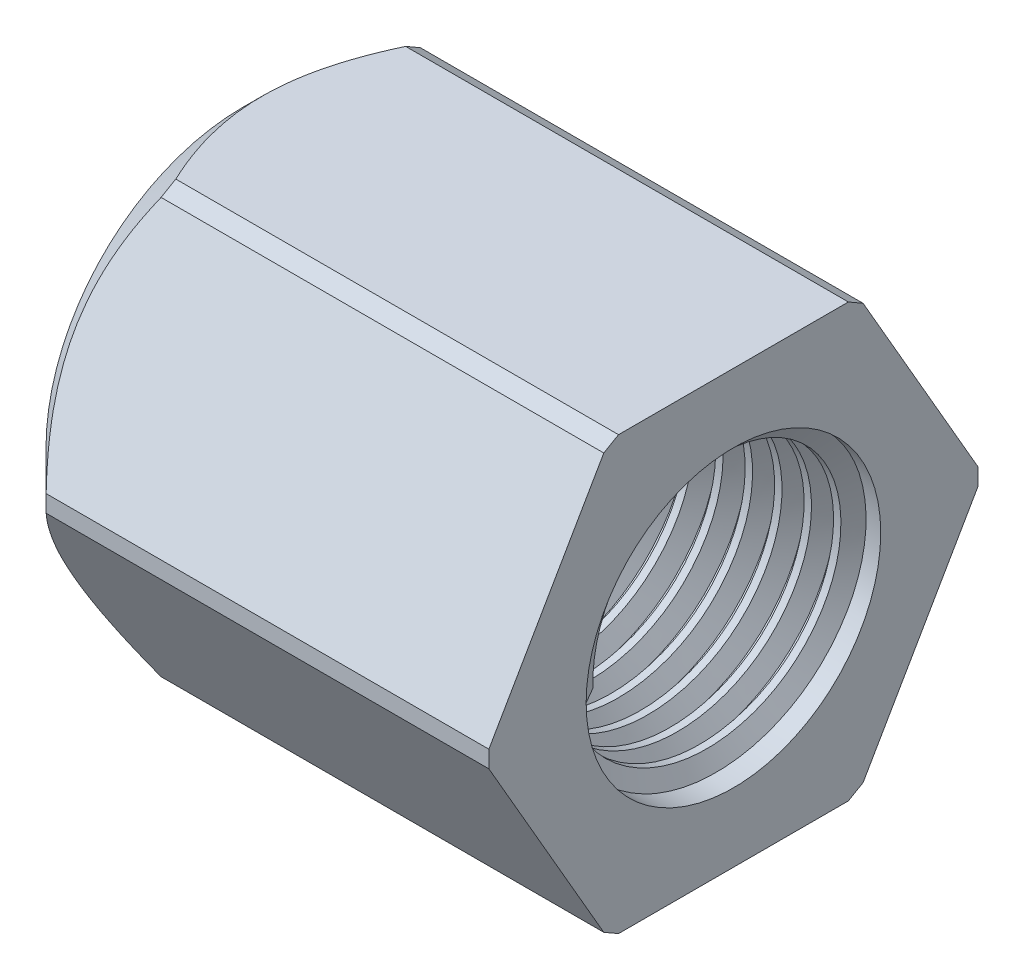
SolidWorks part; units mm, degrees
ref_plane "Спереди" through (0, 0, 0) normal (0, 0, 1) x (1, 0, 0)
ref_plane "Сверху" through (0, 0, 0) normal (0, 1, 0) x (1, 0, 0)
ref_plane "Справа" through (0, 0, 0) normal (1, 0, 0) x (0, 0, -1)
sketch "Эскиз1" plane through (0, 0, 0) normal (1, 0, 0) x (0, 0, -1)
  line L0 (0, 0) -> (33.8712, 0) construction
  line L1 (12.4517, 0.433) -> (6.6009, 10.567)
  line L2 (5.8509, 11) -> (-5.8509, 11)
  line L3 (-6.6009, 10.567) -> (-12.4517, 0.433)
  line L4 (-12.4517, -0.433) -> (-6.6009, -10.567)
  line L5 (-5.8509, -11) -> (5.8509, -11)
  line L6 (6.6009, -10.567) -> (12.4517, -0.433)
  line L7 (6.6009, 10.567) -> (5.8509, 11)
  line L8 (-5.8509, 11) -> (-6.6009, 10.567)
  line L9 (-12.4517, 0.433) -> (-12.4517, -0.433)
  line L10 (-6.6009, -10.567) -> (-5.8509, -11)
  line L11 (5.8509, -11) -> (6.6009, -10.567)
  line L12 (12.4517, -0.433) -> (12.4517, 0.433)
  circle A0 centre (0, 0) radius 11 construction
  circle A1 centre (0, 0) radius 3.5
  point P2 (12.7017, 0)
  point P3 (6.3509, 11)
  point P4 (-6.3509, 11)
  point P5 (-12.7017, 0)
  point P6 (-6.3509, -11)
  point P7 (6.3509, -11)
  dimension "D2" = 7
  dimension "D1" = 22
extrude "Бобышка-Вытянуть1" add sketch "Эскиз1" along normal blind 25
sketch "Эскиз9" plane through (25, 0, 0) normal (1, 0, 0) x (0, 0, -1)
  circle A0 centre (0, 0) radius 7.5
  dimension "D1" = 15
extrude "Вырез-Вытянуть2" cut sketch "Эскиз9" against normal blind 20
thread "Резьба1" pitch 1.5 method extrude profile "Профиль резьбы2" start angle 0, offset 0, length 0, pitch 1.5, diameter 15
ref_plane "Плоскость5" through (25, 0, 7.5) normal (0, -1, 0) x (0, 0, 1)
sketch "Профиль резьбы2" plane through (25, 0, 7.5) normal (0, -1, 0) x (0, 0, 1)
  line L0 (0, 0) -> (0, 1.5) construction
  line L11 (0, 0) -> (0, 1.3125)
  line L12 (0, 1.3125) -> (-0.8119, 0.8437)
  line L13 (-0.8119, 0.8437) -> (-0.8119, 0.4687)
  line L15 (-0.8119, 0.4687) -> (0, 0)
  line L17 (-0.8119, 0.6562) -> (0, 0.6562) construction
  point P2 (0, 0)
  dimension "Pitch" = 1.5
  dimension "Profile_Angle" = 60
  dimension "Profile_Land" = 0.375
  dimension "Profile_Height" = 0.8119
sketch "Эскиз14" plane through (0, 0, 0) normal (-1, 0, 0) x (0, 0, 1)
  line L0 (6.6009, 10.567) -> (12.4517, 0.433) construction
  circle A0 centre (0, 0) radius 10.5
  dimension "D1" = 0.5
sketch "Эскиз15" plane through (0, 0, 0) normal (0, 1, 0) x (1, 0, 0)
  line L0 (0, 10) -> (0, 14)
  line L1 (0, 10.5) -> (0, -10.5) construction
  line L2 (0, 14) -> (4, 14)
  line L3 (4, 14) -> (0, 10)
  dimension "D1" = 45
  dimension "D2" = 4
  dimension "D3" = 10
sweep "Вырез-По траектории1" cut profiles "Эскиз15" path "Эскиз14"
